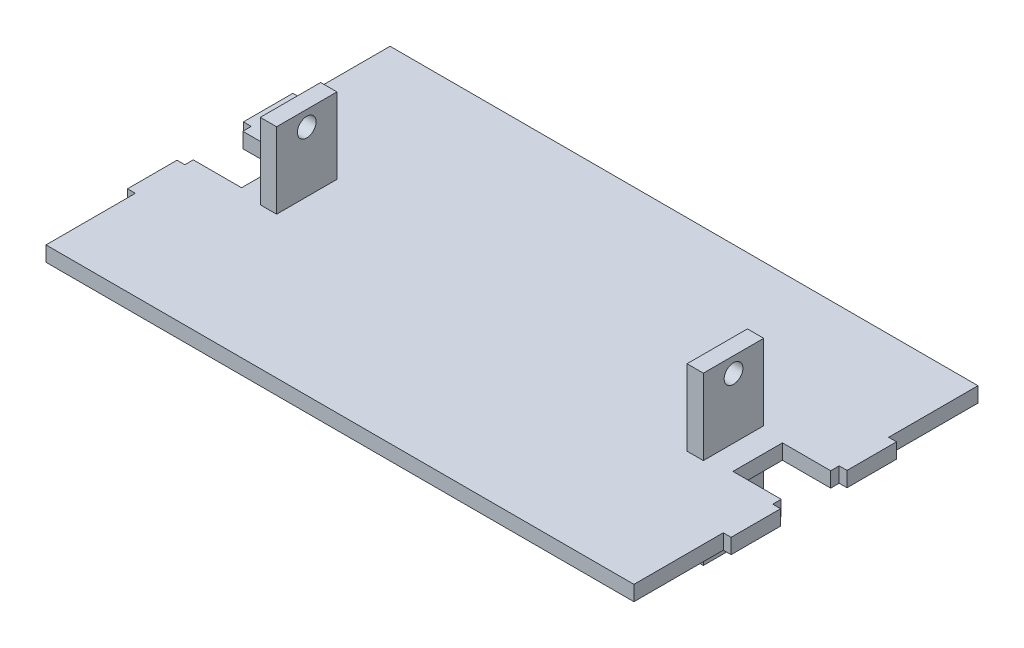
SolidWorks part; units mm, degrees
ref_plane "Front Plane" through (0, 0, 0) normal (0, 0, 1) x (1, 0, 0)
ref_plane "Top Plane" through (0, 0, 0) normal (0, 1, 0) x (1, 0, 0)
ref_plane "Right Plane" through (0, 0, 0) normal (1, 0, 0) x (0, 0, -1)
sketch "Sketch1" plane through (0, 0, 0) normal (0, 1, 0) x (1, 0, 0)
  line L0 (0, 72.39) -> (0, -72.39) construction
  line L1 (123.698, -72.39) -> (-123.698, -72.39)
  line L2 (123.698, -72.39) -> (123.698, -34.798)
  line L3 (123.698, 72.39) -> (-123.698, 72.39)
  line L4 (-123.698, -72.39) -> (-123.698, -34.798)
  line L5 (123.698, -72.39) -> (-123.698, 72.39) construction
  line L6 (123.698, 72.39) -> (-123.698, -72.39) construction
  line L7 (123.698, 10.414) -> (103.378, 10.414)
  line L9 (123.698, -10.414) -> (103.378, -10.414)
  line L10 (103.378, 10.414) -> (103.378, -10.414)
  line L13 (-123.698, -10.414) -> (-103.378, -10.414)
  line L14 (-103.378, 10.414) -> (-103.378, -10.414)
  line L15 (-123.698, 10.414) -> (-103.378, 10.414)
  line L17 (-126.9885, 0) -> (127.0115, 0) construction
  line L18 (-123.698, 13.97) -> (-127, 13.97)
  line L20 (-123.698, 34.798) -> (-127, 34.798)
  line L21 (-127, 13.97) -> (-127, 34.798)
  line L22 (-123.698, -34.798) -> (-127, -34.798)
  line L23 (-127, -13.97) -> (-127, -34.798)
  line L24 (-123.698, -13.97) -> (-127, -13.97)
  line L27 (123.698, -13.97) -> (127, -13.97)
  line L28 (127, -13.97) -> (127, -34.798)
  line L29 (123.698, -34.798) -> (127, -34.798)
  line L30 (123.698, 34.798) -> (127, 34.798)
  line L31 (127, 13.97) -> (127, 34.798)
  line L32 (123.698, 13.97) -> (127, 13.97)
  line L34 (-123.698, 34.798) -> (-123.698, 72.39)
  line L35 (-123.698, -13.97) -> (-123.698, -10.414)
  line L36 (123.698, 34.798) -> (123.698, 72.39)
  line L37 (123.698, -13.97) -> (123.698, -10.414)
  line L38 (-123.698, 10.414) -> (-123.698, 13.97)
  line L39 (123.698, 10.414) -> (123.698, 13.97)
  point P0 (0, 0)
  point P6 (127, 0)
  dimension "D1" = 247.396
  dimension "D2" = 144.78
  dimension "D3" = 20.828
  dimension "D5" = 3.302
  dimension "D6" = 20.828
  dimension "D4" = 20.32
  dimension "D7" = 3.556
  dimension "D8" = 3.556
  dimension "D9" = 3.556
  dimension "D10" = 3.556
  dimension "D11" = 37.592
  dimension "D12" = 20.828
  dimension "D13" = 37.592
extrude "Boss-Extrude1" add sketch "Sketch1" along normal mid plane 6.35
sketch "Sketch2" plane through (0, 0, 0) normal (0, 1, 0) x (1, 0, 0)
  line L0 (-103.378, 10.414) -> (-103.378, -10.414) construction
  line L1 (86.36, -12.7) -> (93.218, -12.7)
  line L2 (86.36, -12.7) -> (86.36, 12.7)
  line L3 (86.36, 12.7) -> (93.218, 12.7)
  line L4 (93.218, -12.7) -> (93.218, 12.7)
  line L5 (86.36, -12.7) -> (93.218, 12.7) construction
  line L6 (86.36, 12.7) -> (93.218, -12.7) construction
  line L9 (-86.36, -12.7) -> (-86.36, 12.7)
  line L10 (-86.36, 12.7) -> (-93.218, 12.7)
  line L11 (-93.218, -12.7) -> (-93.218, 12.7)
  line L12 (-86.36, -12.7) -> (-93.218, -12.7)
  line L13 (103.378, -10.414) -> (103.378, 10.414) construction
  point P0 (89.789, 0)
  point P10 (103.378, 0)
  dimension "D1" = 10.16
  dimension "D2" = 10.16
  dimension "D3" = 25.4
  dimension "D4" = 25.4
  dimension "D5" = 6.858
  dimension "D6" = 6.858
  dimension "D7" = 6.858
extrude "Boss-Extrude2" add sketch "Sketch2" along normal mid plane 70.104
sketch "Sketch3" plane through (-93.218, 0, 0) normal (-1, 0, 0) x (0, 0, 1)
  line L0 (12.7, 3.175) -> (-12.7, 3.175) construction
  line L1 (12.7, -3.175) -> (-12.7, -3.175) construction
  circle A0 centre (0, 28.575) radius 3.937
  circle A1 centre (0, -28.575) radius 3.937
  dimension "D1" = 7.874
  dimension "D2" = 7.874
  dimension "D3" = 25.4
  dimension "D4" = 25.4
extrude "Cut-Extrude1" cut sketch "Sketch3" against normal through all both and the other way through all
equation "\"length\"=9.74"
equation "\"width\"=5.7"
equation "\"height\"= 0.25"
equation "\"D1@Sketch1\"=\"length\""
equation "\"D2@Sketch1\"=\"width\""
equation "\"eyebolt width\"= 0.82"
equation "\"eyebolt length\"= 0.8"
equation "\"D3@Sketch1\"=\"eyebolt width\""
equation "\"D4@Sketch1\"=\"eyebolt length\""
equation "\"lead screw holder height\"= 2.76"
equation "\"lead screw diameter\"= 0.31"
equation "\"D1@Sketch3\"=\"lead screw diameter\""
equation "\"distance from holders to board\"=0.4"
equation "\"D2@Sketch3\"=\"lead screw diameter\""
equation "\"Lead_Screw_Dist\" = 2.25in"
equation "\"D3@Sketch3\"=(\"Lead_Screw_Dist\"-\"height\")/2"
equation "\"D4@Sketch3\"=(\"Lead_Screw_Dist\"-\"height\")/2"
